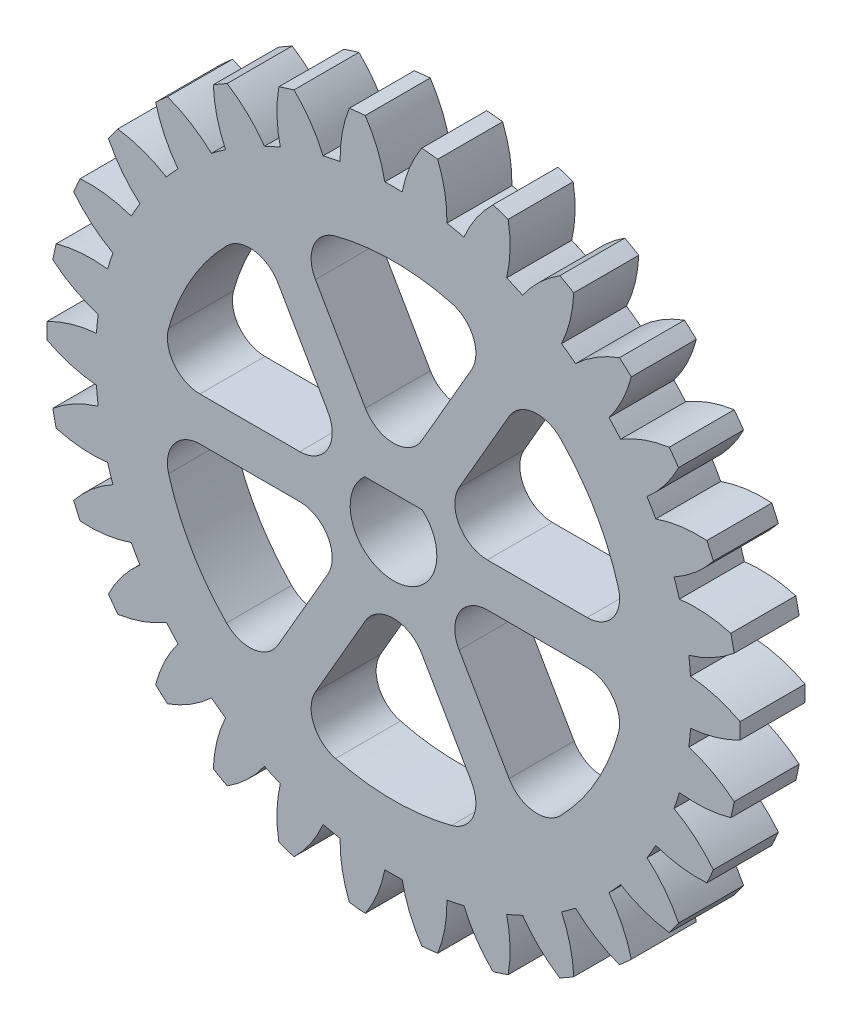
SolidWorks part; units mm, degrees
ref_plane "Front Plane" through (0, 0, 0) normal (0, 0, 1) x (1, 0, 0)
ref_plane "Top Plane" through (0, 0, 0) normal (0, 1, 0) x (1, 0, 0)
ref_plane "Right Plane" through (0, 0, 0) normal (1, 0, 0) x (0, 0, -1)
sketch "Sketch1" plane through (0, 0, 0) normal (0, 0, 1) x (1, 0, 0)
  circle A1 centre (0, 0) radius 16
  dimension "addendumDiameter" = 32
extrude "Boss-Extrude1" add sketch "Sketch1" along normal blind 3
sketch "Sketch2" plane through (0, 0, 3) normal (0, 0, 1) x (1, 0, 0)
  line L0 (0, 0) -> (0, 31) construction
  line L1 (0, 0) -> (-2.7303, 25.9775) construction
  line L2 (-0.7804, 14.9797) -> (-1.5658, 14.8971) construction
  circle A0 centre (0, 0) radius 14.0954 construction
  circle A1 centre (0, 0) radius 15 construction
  circle A2 centre (0, 0) radius 13.75 construction
  arc A5 (1.3054, 15.9467) -> (0.4013, 13.7441) centre (6.2936, 12.6123) ccw
  arc A8 (1.3054, 15.9467) -> (-1.3054, 15.9467) centre (0, 0) ccw
  circle A9 centre (0, 0) radius 16 construction
  arc A10 (0.4013, 13.7441) -> (-0.4013, 13.7441) centre (0, 0) ccw
  circle A11 centre (0, 0) radius 16 construction
  arc A12 (-1.3054, 15.9467) -> (-0.4013, 13.7441) centre (-6.2936, 12.6123) cw
  dimension "Dedendum Circle" = 27.5
  dimension "Base Diameter" = 28.1908
  dimension "D7" = 30
  dimension "D4" = 6
  dimension "D1" = 6
  dimension "D3" = 6
  dimension "D2" = 0.7854
extrude "Cut-Extrude1" cut sketch "Sketch2" against normal blind 3
pattern_circular "CirPattern1" count 30 over 360 about axis through (0, 0, 3) along (0, 0, 1) of "Cut-Extrude1"
sketch "Sketch3" plane through (0, 0, 3) normal (0, 0, 1) x (1, 0, 0)
  line L0 (0, 0) -> (0, 26.8242) construction
  line L1 (-9.6877, 2) -> (9.6877, 2) construction
  line L2 (0, 2) -> (4.5, 9.7942)
  line L4 (-4.5, 9.7942) -> (0, 2)
  arc A0 (-4.5, 9.7942) -> (4.5, 9.7942) centre (0, 0) cw
  arc A3 (3.2501, 13.3604) -> (2.465, 13.5272) centre (0, 0) ccw construction
  dimension "D1" = 2
  dimension "D4" = 9
extrude "Cut-Extrude2" cut sketch "Sketch3" against normal through all
fillet "Fillet2" radius 1.5 3 edges at (-4.5, 9.7942, 1.5) (0, 2, 1.5) (4.5, 9.7942, 1.5)
ref_axis "Axis1" through (0, 0, 0) along (0, 0, 1)
pattern_circular "CirPattern3" count 6 over 360 about axis through (0, 0, 0) along (0, 0, 1) of "Cut-Extrude2", "Fillet2"
sketch "Sketch4" plane through (0, 0, 3) normal (0, 0, 1) x (1, 0, 0)
  line L0 (-1.3229, 1.5) -> (1.3229, 1.5)
  arc A0 (-1.3229, 1.5) -> (1.3229, 1.5) centre (0, 0) ccw
  dimension "D1" = 4
  dimension "D2" = 1.5
extrude "Cut-Extrude3" cut sketch "Sketch4" against normal through all
equation "\"module\"= 1.0"
equation "\"teeth\"= 30"
equation "\"pressureAngle\"= 20deg"
equation "\"gearThickness\"= 3"
equation "\"addendumFactor\"= 1"
equation "\"dedendumFactor\"= 1.25"
equation "\"pitch\"= 1 / \"module\""
equation "\"pitchDiameter\"= \"teeth\" / \"pitch\""
equation "\"addendum\"= \"addendumFactor\" / \"pitch\""
equation "\"dedendum\"= \"dedendumFactor\" / \"pitch\""
equation "\"D1@Boss-Extrude1\"=\"gearThickness\""
equation "\"D3@Sketch2\"=180/\"teeth\""
equation "\"addendumDiameter@Sketch1\"=\"pitchDiameter\" + 2 * \"addendum\""
equation "\"Dedendum Circle@Sketch2\" = \"pitchDiameter\" - 2 * \"dedendum\""
equation "\"Base Diameter@Sketch2\" = \"pitchDiameter\" * cos ( \"pressureAngle\" ) "
equation "\"D7@Sketch2\"= \"pitchDiameter\""
equation "\"D4@Sketch2\"= \"pitchDiameter\" / 5"
equation "\"D1@Sketch2\"= \"pitchDiameter\" / 5"
equation "\"D2@Sketch2\"= PI / 2 / \"pitch\" / 2"
equation "\"D1@CirPattern1\"= \"teeth\""
